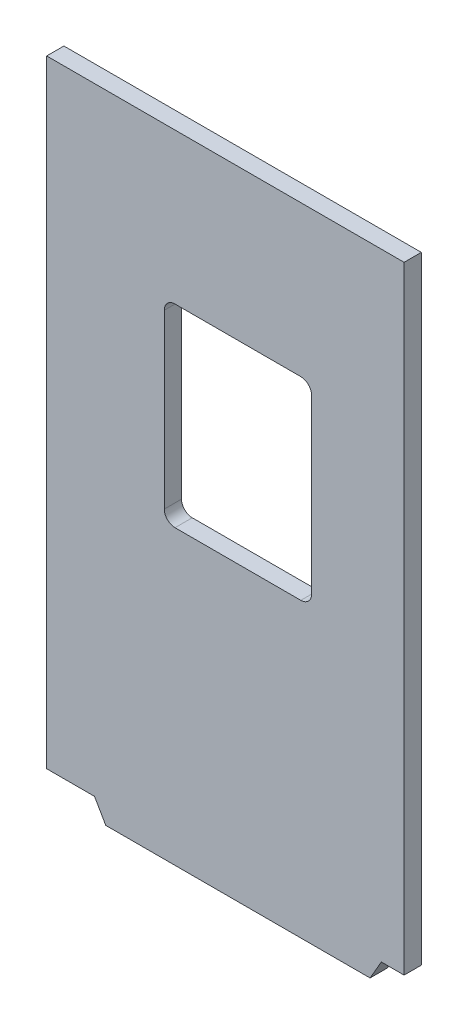
SolidWorks part; units mm, degrees
ref_plane "Front Plane" through (0, 0, 0) normal (0, 0, 1) x (1, 0, 0)
ref_plane "Top Plane" through (0, 0, 0) normal (0, 1, 0) x (1, 0, 0)
ref_plane "Right Plane" through (0, 0, 0) normal (1, 0, 0) x (0, 0, -1)
sketch "Sketch1" plane through (0, 0, 0) normal (0, 0, 1) x (1, 0, 0)
  line L1 (-10, 15) -> (10, 15)
  line L2 (-10, 15) -> (-10, -15)
  line L3 (-10, -15) -> (10, -15)
  line L4 (10, 15) -> (10, -15)
  line L5 (-10, 15) -> (10, -15) construction
  line L6 (-10, -15) -> (10, 15) construction
  point P0 (0, 0)
  dimension "D1" = 30
  dimension "D2" = 20
extrude "Boss-Extrude1" add sketch "Sketch1" along normal blind 1.6
sketch "Sketch2" plane through (-10, 0, 0) normal (-1, 0, 0) x (0, 0, 1)
  line L4 (0, 15) -> (0, -15)
  line L5 (0, -15) -> (1.6, -15)
  line L6 (1.6, -15) -> (1.6, 15)
  line L7 (1.6, 15) -> (0, 15)
  line L8 (0, 15) -> (0, -15)
  line L9 (0, -15) -> (1.6, -15)
  line L10 (1.6, -15) -> (1.6, 15)
  line L11 (1.6, 15) -> (0, 15)
  dimension "D1" = 0
extrude "Boss-Extrude2" add sketch "Sketch2" along normal up to vertex (13.2296 mm away)
sketch "Sketch3" plane through (0, 15, 0) normal (0, 1, 0) x (1, 0, 0)
  line L4 (10, 0) -> (-23.2296, 0)
  line L5 (-23.2296, 0) -> (-23.2296, -1.6)
  line L6 (-23.2296, -1.6) -> (10, -1.6)
  line L7 (10, -1.6) -> (10, 0)
  line L8 (10, 0) -> (-23.2296, 0)
  line L9 (-23.2296, 0) -> (-23.2296, -1.6)
  line L10 (-23.2296, -1.6) -> (10, -1.6)
  line L11 (10, -1.6) -> (10, 0)
  dimension "D1" = 0
extrude "Boss-Extrude3" add sketch "Sketch3" along normal blind 29.21
sketch "Sketch4" plane through (0, 0, 0) normal (0, 0, -1) x (-1, 0, 0)
  line L0 (-0.6488, 12.94) -> (-0.6488, 29.45) construction
  line L1 (-0.6488, 12.94) -> (-0.6488, 29.45) construction
  line L2 (11.5481, 29.45) -> (11.5481, 12.94) construction
  line L3 (11.5481, 29.45) -> (11.5481, 12.94) construction
  line L6 (11.5481, 12.94) -> (-0.6488, 12.94) construction
  line L7 (11.5481, 12.94) -> (-0.6488, 12.94) construction
  line L8 (-1.3988, 13.19) -> (-1.3988, 29.2)
  line L10 (-0.3988, 30.2) -> (11.2981, 30.2)
  line L11 (-0.6488, 29.45) -> (11.5481, 29.45) construction
  line L12 (12.2981, 29.2) -> (12.2981, 13.19)
  line L13 (11.2981, 12.19) -> (-0.3988, 12.19)
  line L14 (12.2981, 30.2) -> (12.2981, 12.19) construction
  line L15 (12.2981, 12.19) -> (-1.3988, 12.19) construction
  line L16 (-1.3988, 30.2) -> (12.2981, 30.2) construction
  line L17 (-1.3988, 12.19) -> (-1.3988, 30.2) construction
  arc A0 (12.2981, 13.19) -> (11.2981, 12.19) centre (11.2981, 13.19) cw
  arc A1 (11.2981, 30.2) -> (12.2981, 29.2) centre (11.2981, 29.2) cw
  arc A2 (-1.3988, 29.2) -> (-0.3988, 30.2) centre (-0.3988, 29.2) cw
  arc A3 (-1.3988, 13.19) -> (-0.3988, 12.19) centre (-0.3988, 13.19) ccw
  dimension "D2" = 1
  dimension "D1" = 0.75
extrude "Cut-Extrude1" cut sketch "Sketch4" against normal up to surface (1.6 mm away) up to face at (-6.6148, 14.605, 1.6)
sketch "Sketch5" plane through (0, 0, 0) normal (0, 0, -1) x (-1, 0, 0)
  line L0 (-7.884, -13.1868) -> (-6.4805, -15.6176) construction
  line L1 (-10, -13.1868) -> (-7.884, -13.1868) construction
  line L2 (-7.884, -13.1868) -> (-6.8371, -15)
  line L3 (-10, -13.1868) -> (-7.884, -13.1868)
  line L4 (17.3797, -15.6176) -> (18.7832, -13.1868) construction
  line L5 (19.6396, -13.1868) -> (22.596, -13.1868) construction
  line L6 (18.7832, -13.1868) -> (19.6396, -13.1868) construction
  line L7 (17.7363, -15) -> (18.7832, -13.1868)
  line L8 (19.6396, -13.1868) -> (23.2296, -13.1868)
  line L9 (18.7832, -13.1868) -> (19.6396, -13.1868)
  line L10 (23.2296, -15) -> (-10, -15) construction
  line L11 (-10, -15) -> (-10, 44.21) construction
  line L12 (23.2296, -15) -> (17.7363, -15)
  line L13 (-10, -15) -> (-10, -13.1868)
  line L14 (23.2296, 44.21) -> (23.2296, -15) construction
  line L15 (23.2296, -13.1868) -> (23.2296, -15)
  line L16 (-6.8371, -15) -> (-10, -15)
extrude "Cut-Extrude2" cut sketch "Sketch5" against normal blind 29.21
